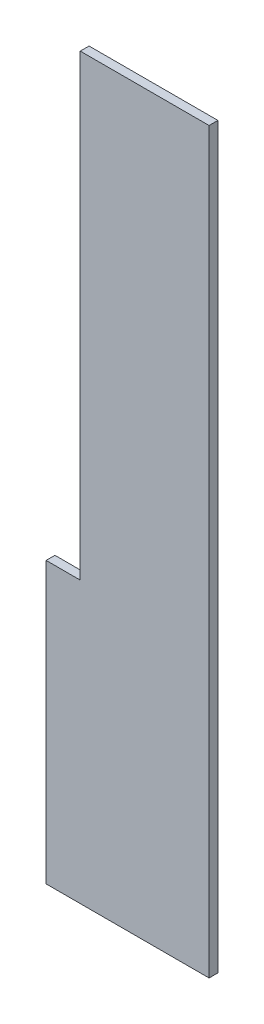
SolidWorks part; units mm, degrees
ref_plane "Ön Düzlem" through (0, 0, 0) normal (0, 0, 1) x (1, 0, 0)
ref_plane "Üst Düzlem" through (0, 0, 0) normal (0, 1, 0) x (1, 0, 0)
ref_plane "Sağ Düzlem" through (0, 0, 0) normal (1, 0, 0) x (0, 0, -1)
sketch "Çizim1" plane through (0, 0, 0) normal (0, 0, 1) x (1, 0, 0)
  line L0 (0, 0) -> (0, -3465)
  line L1 (0, -3465) -> (-660, -3465)
  line L2 (-660, -3465) -> (-660, -6005)
  line L3 (-660, -6005) -> (1360, -6005)
  line L4 (1360, -6005) -> (1360, 0)
  line L5 (1360, 0) -> (0, 0)
  dimension "D1" = 2540
  dimension "D2" = 660
  dimension "D3" = 1360
  dimension "D4" = 3465
  dimension "D5" = 6005
  dimension "D6" = 2020
base flange "Taban-Flanş1" sketch "Çizim1" thickness 40 reverse thickness direction no parameters "D1"=10
sketch "Çizim2" plane through (0, 0, 0) normal (0, 0, 1) x (1, 0, 0)
  line L0 (1360, -6005) -> (1360, 0) construction
  line L1 (0, 0) -> (1360, 0)
  line L2 (0, 0) -> (0, -355)
  line L3 (0, -355) -> (1360, -355)
  line L4 (1360, 0) -> (1360, -355)
  line L5 (0, -3465) -> (-660, -3465) construction
  dimension "D1" = 3110
  dimension "D2" = 355
  dimension "D3" = 1360
extrude "Kes-Ekstrüzyon1" cut sketch "Çizim2" against normal through all both and the other way through all
sketch "Çizim3" plane through (0, 0, 0) normal (0, 0, 1) x (1, 0, 0)
  line L0 (0, -355) -> (1360, -355) construction
  line L1 (0, -3465) -> (365, -3465)
  line L2 (0, -3465) -> (0, -355)
  line L3 (0, -355) -> (365, -355)
  line L4 (365, -3465) -> (365, -355)
  line L5 (-660, -3465) -> (-660, -6005) construction
  line L6 (1360, -6005) -> (1360, -355) construction
  line L7 (-660, -6005) -> (1360, -6005) construction
  line L8 (1360, -355) -> (1355, -355)
  line L9 (1360, -355) -> (1360, -6005)
  line L10 (1360, -6005) -> (1355, -6005)
  line L11 (1355, -355) -> (1355, -6005)
  dimension "D1" = 365
  dimension "D2" = 1025
  dimension "D3" = 3110
  dimension "D4" = 995
  dimension "D5" = 990
extrude "Kes-Ekstrüzyon2" cut sketch "Çizim3" against normal through all both and the other way through all
sketch "Çizim4" plane through (0, 0, 0) normal (0, 0, 1) x (1, 0, 0)
  line L0 (365, -355) -> (1355, -355) construction
  line L1 (770, -355) -> (365, -355)
  line L2 (770, -355) -> (770, -3465)
  line L3 (770, -3465) -> (365, -3465)
  line L4 (365, -355) -> (365, -3465)
  line L5 (1355, -355) -> (1355, -6005) construction
  line L6 (-660, -3465) -> (-660, -6005) construction
  dimension "D1" = 585
  dimension "D2" = 3110
  dimension "D3" = 1430
extrude "Kes-Ekstrüzyon3" cut sketch "Çizim4" against normal through all both and the other way through all
sketch "Çizim5" plane through (0, 0, 0) normal (0, 0, 1) x (1, 0, 0)
  line L0 (615, -3465) -> (615, -4737)
  line L1 (770, -3465) -> (-660, -3465) construction
  line L2 (615, -4737) -> (1355, -4737)
  line L3 (1355, -355) -> (1355, -6005) construction
  line L4 (-660, -3465) -> (-660, -6005) construction
  line L5 (-660, -6005) -> (1355, -6005) construction
  line L6 (770, -3465) -> (770, -355) construction
  line L7 (615, -3465) -> (-660, -3465)
  line L8 (-660, -3465) -> (-660, -6005)
  line L9 (-660, -6005) -> (1355, -6005)
  line L10 (1355, -6005) -> (1355, -4737)
  dimension "D1" = 1275
  dimension "D2" = 1268
  dimension "D3" = 155
  dimension "D4" = 740
  dimension "D5" = 1272
  dimension "D6" = 2540
extrude "Kes-Ekstrüzyon4" cut sketch "Çizim5" against normal through all both and the other way through all
sketch "Çizim6" plane through (0, 0, 0) normal (0, 0, 1) x (1, 0, 0)
  line L0 (1355, -355) -> (1355, -4737) construction
  line L1 (770, -355) -> (1355, -355)
  line L2 (770, -355) -> (770, -1385)
  line L3 (770, -1385) -> (1355, -1385)
  line L4 (1355, -355) -> (1355, -1385)
  line L5 (770, -3465) -> (615, -3465) construction
  line L6 (615, -4737) -> (615, -3465) construction
  dimension "D1" = 585
  dimension "D2" = 2080
  dimension "D3" = 1030
  dimension "D4" = 155
  dimension "D5" = 740
extrude "Kes-Ekstrüzyon5" cut sketch "Çizim6" against normal through all both and the other way through all
sketch "Büküm-Çizgileri1" [suppressed] plane through (0, 0, 0) normal (0, 1, 0) x (1, 0, 0)
sketch "Sınırlandırma-Kutusu1" [suppressed] plane through (0, 0, 0) normal (0, 1, 0) x (1, 0, 0)
sheet metal parameters "Sac-Levha1" thickness 40 parameters "D1"=10
flat pattern "Düz-Çoğaltma1" [suppressed]
sketch "Büküm-Çizgileri2" plane through (0, 0, 0) normal (0, 1, 0) x (1, 0, 0)
sketch3d "Sınırlandırma-Kutusu2" [suppressed]
  line L0 (1360, 0, 0) -> (1360, -6005, 0) construction
  line L1 (-660, 0, 0) -> (-660, -6005, 0) construction
  line L2 (1360, 0, 0) -> (-660, 0, 0) construction
  line L3 (1360, -6005, 0) -> (-660, -6005, 0) construction
sheet metal parameters "Sac-Levha2" thickness 40 parameters "D1"=10
flat pattern "Düz-Çoğaltma1"
sketch "Büküm-Çizgileri2" plane through (0, 0, 0) normal (0, 1, 0) x (1, 0, 0)
sketch3d "Sınırlandırma-Kutusu2" [suppressed]
  line L0 (1360, -355, 0) -> (1360, -6005, 0) construction
  line L1 (-660, -355, 0) -> (-660, -6005, 0) construction
  line L2 (1360, -355, 0) -> (-660, -355, 0) construction
  line L3 (1360, -6005, 0) -> (-660, -6005, 0) construction
sheet metal parameters "Sac-Levha3" thickness 40 parameters "D1"=10
flat pattern "Düz-Çoğaltma1"
sketch "Büküm-Çizgileri2" plane through (0, 0, 0) normal (0, 1, 0) x (1, 0, 0)
sketch3d "Sınırlandırma-Kutusu2" [suppressed]
  line L0 (1355, -355, 0) -> (1355, -6005, 0) construction
  line L1 (-660, -355, 0) -> (-660, -6005, 0) construction
  line L2 (1355, -355, 0) -> (-660, -355, 0) construction
  line L3 (1355, -6005, 0) -> (-660, -6005, 0) construction
sheet metal parameters "Sac-Levha4" thickness 40 parameters "D1"=10
flat pattern "Düz-Çoğaltma1"
sketch "Büküm-Çizgileri2" plane through (0, 0, 0) normal (0, 1, 0) x (1, 0, 0)
sketch3d "Sınırlandırma-Kutusu2" [suppressed]
  line L0 (1355, -355, 0) -> (1355, -6005, 0) construction
  line L1 (-660, -355, 0) -> (-660, -6005, 0) construction
  line L2 (1355, -355, 0) -> (-660, -355, 0) construction
  line L3 (1355, -6005, 0) -> (-660, -6005, 0) construction
sheet metal parameters "Sac-Levha5" thickness 40 parameters "D1"=10
flat pattern "Düz-Çoğaltma1"
sketch "Büküm-Çizgileri2" plane through (0, 0, 0) normal (0, 1, 0) x (1, 0, 0)
sketch3d "Sınırlandırma-Kutusu2" [suppressed]
  line L0 (1355, -355, 0) -> (1355, -4737, 0) construction
  line L1 (615, -355, 0) -> (615, -4737, 0) construction
  line L2 (1355, -355, 0) -> (615, -355, 0) construction
  line L3 (1355, -4737, 0) -> (615, -4737, 0) construction
sheet metal parameters "Sac-Levha6" thickness 40 parameters "D1"=10
flat pattern "Düz-Çoğaltma1"
sketch "Büküm-Çizgileri2" plane through (0, 0, 0) normal (0, 1, 0) x (1, 0, 0)
sketch3d "Sınırlandırma-Kutusu2" [suppressed]
  line L0 (1355, -1385, 0) -> (1355, -4737, 0) construction
  line L1 (615, -1385, 0) -> (615, -4737, 0) construction
  line L2 (1355, -1385, 0) -> (615, -1385, 0) construction
  line L3 (1355, -4737, 0) -> (615, -4737, 0) construction
